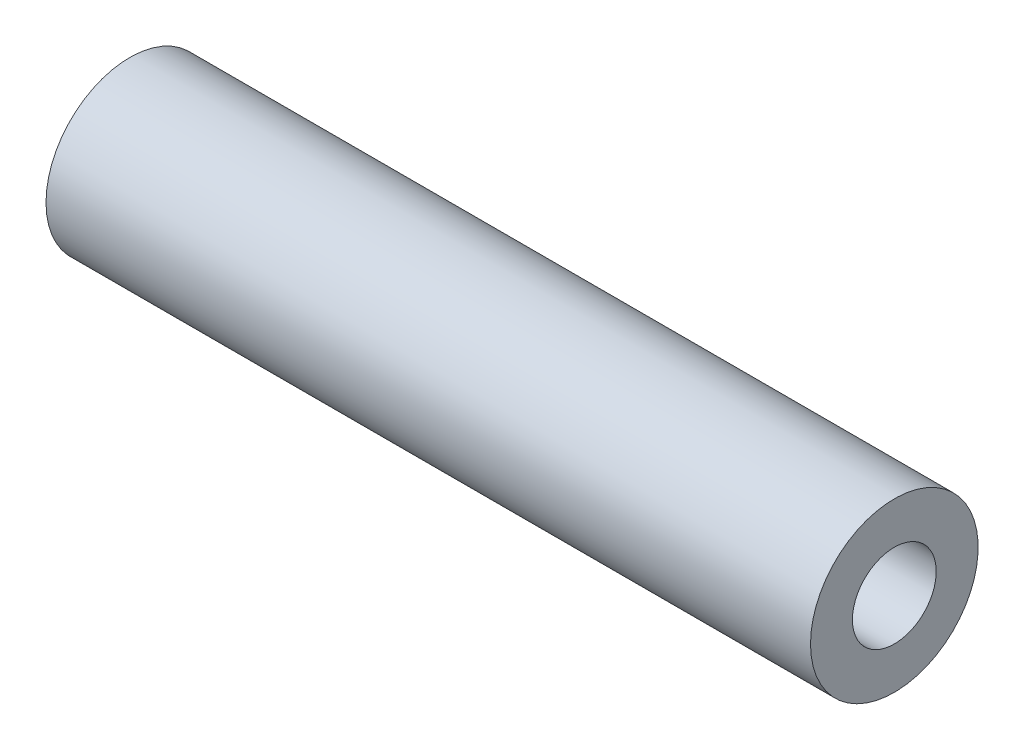
SolidWorks part; units mm, degrees
ref_plane "Front Plane" through (0, 0, 0) normal (0, 0, 1) x (1, 0, 0)
ref_plane "Top Plane" through (0, 0, 0) normal (0, 1, 0) x (1, 0, 0)
ref_plane "Right Plane" through (0, 0, 0) normal (1, 0, 0) x (0, 0, -1)
sketch "Sketch1" plane through (0, 0, 0) normal (0, 0, 1) x (1, 0, 0)
  line L0 (-10.3053, 0) -> (24.5678, 0) construction
  line L1 (0, 0) -> (0, 2.5)
  line L2 (0, 2.5) -> (22.8, 2.5)
  line L3 (22.8, 2.5) -> (22.8, 0)
  line L4 (22.8, 0) -> (0, 0)
  dimension "D1" = 5
  dimension "D2" = 22.8
revolve "Revolve1" add sketch "Sketch1" angle 360 about L0
hole_wizard "M3x0.5 Tapped Hole1" positions "Sketch2" profile "Sketch3" tap size "M3x0.5" standard "ANSI Metric" end condition through all
sketch "Sketch2" plane through (0, 0, 0) normal (-1, 0, 0) x (0, 0, 1)
  point P0 (0, 0)
sketch "Sketch3" plane through (0, 0, 0) normal (0, 1, 0) x (0, 0, 1)
  line L0 (0, 0) -> (0, 22.8)
  line L1 (0, 22.8) -> (1.25, 22.8)
  line L2 (1.25, 22.8) -> (1.25, 0)
  line L5 (1.25, 0) -> (0, 0)
  line L11 (0, -6.35) -> (0, 107.95) construction
  dimension "Thread Major Dia." = 2.5
  dimension "Thru Tap Drill Depth" = 22.8
